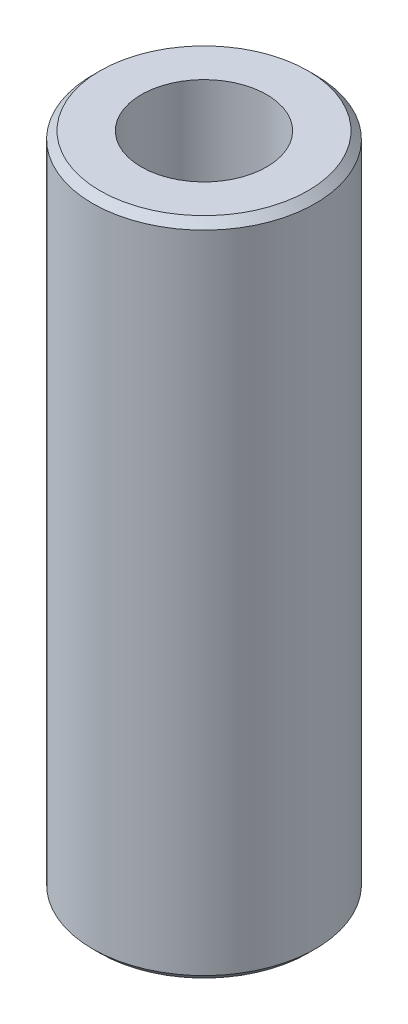
SolidWorks part; units mm, degrees
ref_plane "Front Plane" through (0, 0, 0) normal (0, 0, 1) x (1, 0, 0)
ref_plane "Top Plane" through (0, 0, 0) normal (0, 1, 0) x (1, 0, 0)
ref_plane "Right Plane" through (0, 0, 0) normal (1, 0, 0) x (0, 0, -1)
sketch "Sketch1" plane through (0, 0, 0) normal (0, 1, 0) x (1, 0, 0)
  circle A0 centre (0, 0) radius 12.5
  dimension "SHAFT_OD" = 25
extrude "Boss-Extrude1" add sketch "Sketch1" along normal blind 74.1376
sketch "Sketch2" plane through (0, 0, 0) normal (0, 1, 0) x (1, 0, 0)
  circle A0 centre (0, 0) radius 7.0406
  dimension "BORE_D" = 14.0813
extrude "Cut-Extrude1" cut sketch "Sketch2" along normal through all
chamfer "Chamfer1" distance 0.8275 angle 45 2 edges at (0, 74.1376, 12.5) (0, 0, 12.5)
